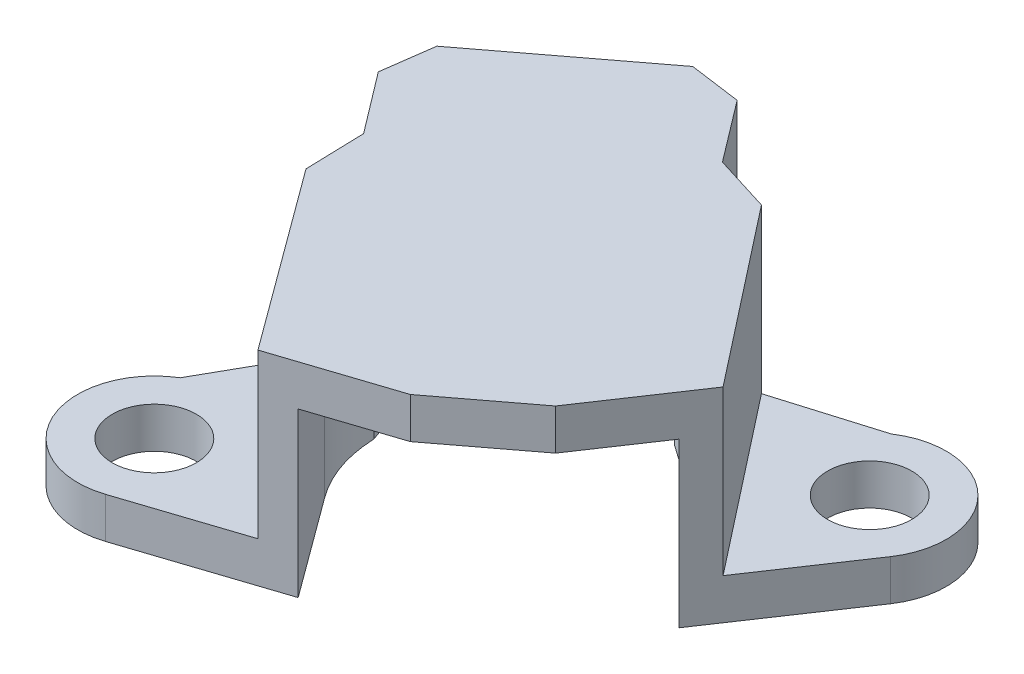
SolidWorks part; units mm, degrees
ref_plane "Front Plane" through (0, 0, 0) normal (0, 0, 1) x (1, 0, 0)
ref_plane "Top Plane" through (0, 0, 0) normal (0, 1, 0) x (1, 0, 0)
ref_plane "Right Plane" through (0, 0, 0) normal (1, 0, 0) x (0, 0, -1)
sketch "Sketch1" plane through (0, 0, 0) normal (0, 1, 0) x (1, 0, 0)
  line L0 (-12.9702, -5.7861) -> (-10.1498, -0.7856)
  line L1 (-10.1498, -0.7856) -> (-10.2561, 2.9024)
  line L2 (-10.2561, 2.9024) -> (-13.1267, 6.6879)
  line L3 (-13.1267, 6.6879) -> (-12.6865, 9.8906)
  line L4 (-12.6865, 9.8906) -> (-3.6398, 16.7511)
  line L5 (-3.6398, 16.7511) -> (-0.437, 16.3109)
  line L6 (-0.437, 16.3109) -> (2.4336, 12.5254)
  line L7 (2.4336, 12.5254) -> (5.9562, 11.4281)
  line L8 (5.9562, 11.4281) -> (12.1652, 13.2953)
  line L9 (-12.1687, 8.2896) -> (-6.6474, 0.771)
  line L10 (-9.0173, -14.3855) -> (5.2442, -9.6909)
  line L11 (5.2442, -9.6909) -> (10.3781, -5.7976)
  line L12 (10.3781, -5.7976) -> (18.7463, 6.6684)
  line L13 (-6.6474, 0.771) -> (-6.1841, -0.5369)
  line L14 (-12.1687, 8.2896) -> (-1.8925, 15.8358)
  line L15 (-1.8925, 15.8358) -> (3.5125, 8.4755)
  line L16 (3.5125, 8.4755) -> (4.6469, 7.6765)
  line L17 (-10.1498, -0.7856) -> (-1.8866, -12.0382)
  line L18 (5.9562, 11.4281) -> (14.5622, 0.4354)
  line L19 (2.1428, -0.2695) -> (-4.5723, -5.2007)
  line L20 (2.1428, -0.2695) -> (8.8579, 4.6617)
  line L21 (-4.5723, -5.2007) -> (-0.0058, -11.4191)
  line L22 (8.8579, 4.6617) -> (13.4563, -1.212)
  circle A0 centre (-10.5064, -9.8618) radius 4.7625
  circle A1 centre (14.7921, 9.3228) radius 4.7625
  circle A2 centre (-10.5064, -9.8618) radius 2.6162
  circle A3 centre (14.7921, 9.3228) radius 2.6162
  arc A4 (-6.1841, -0.5369) -> (4.6469, 7.6765) centre (2.1428, -0.2695) ccw
  point P27 (0, 0)
  dimension "D1" = 8.3312
  dimension "D2" = 15.875
  dimension "D3" = 6.209
  dimension "D4" = 15.0143
  dimension "D5" = 5.741
  dimension "D6" = 12.6492
  dimension "D7" = 14.2615
extrude "Boss-Extrude1" add sketch "Sketch1" along normal blind 2.54 contours A0 L10 L17 L0 | A0 A2 | A1 A3 | A1 L8 L18 L12 region at (-11.4072, 0, 3.372) region at (-8.233, 0, 5.8309) region at (10.402, 0, -6.0435) region at (11.5084, 0, -6.0618)
extrude "Boss-Extrude2" add sketch "Sketch1<5>" along normal blind 12.7 contours L18 L7 L6 L5 L4 L3 L2 L1 L17 L10 L11 L12 A4 L13 L9 L14 L15 L16 region at (-9.8037, 0, -1.0699)
sketch "Sketch1<5>" plane through (0, 0, 0) normal (0, 1, 0) x (1, 0, 0) same geometry as "Sketch1"
extrude "Boss-Extrude3" add sketch "Sketch1<6>" along normal blind 12.7 contours L13 A4 L16 L15 L14 L9 | L9 L13 A4 L16 L15 L14 region at (-2.2223, 0, -5.5782)
sketch "Sketch1<6>" plane through (0, 0, 0) normal (0, 1, 0) x (1, 0, 0) same geometry as "Sketch1"
extrude "Cut-Extrude1" cut sketch "Sketch1<8>" along normal blind 10.16 contours L13 A4 L16 L15 L14 L9 | L9 L13 A4 L16 L15 L14 region at (-2.2223, 0, -5.5782)
sketch "Sketch1<8>" plane through (0, 0, 0) normal (0, 1, 0) x (1, 0, 0) same geometry as "Sketch1"
extrude "Boss-Extrude5" add sketch "Sketch1<9>" along normal up to surface (12.7 mm away) contours A4 L21 L10 L11 L12 L22 region at (-2.0943, 0, 8.1669) up to face at (-0.4688, 12.7, -3.1588)
sketch "Sketch1<9>" plane through (0, 0, 0) normal (0, 1, 0) x (1, 0, 0) same geometry as "Sketch1"
extrude "Cut-Extrude2" cut sketch "Sketch1<11>" along normal blind 10.16 contours A4 L21 L10 L11 L12 L22 region at (-2.0943, 0, 8.1669)
sketch "Sketch1<11>" plane through (0, 0, 0) normal (0, 1, 0) x (1, 0, 0) same geometry as "Sketch1"
